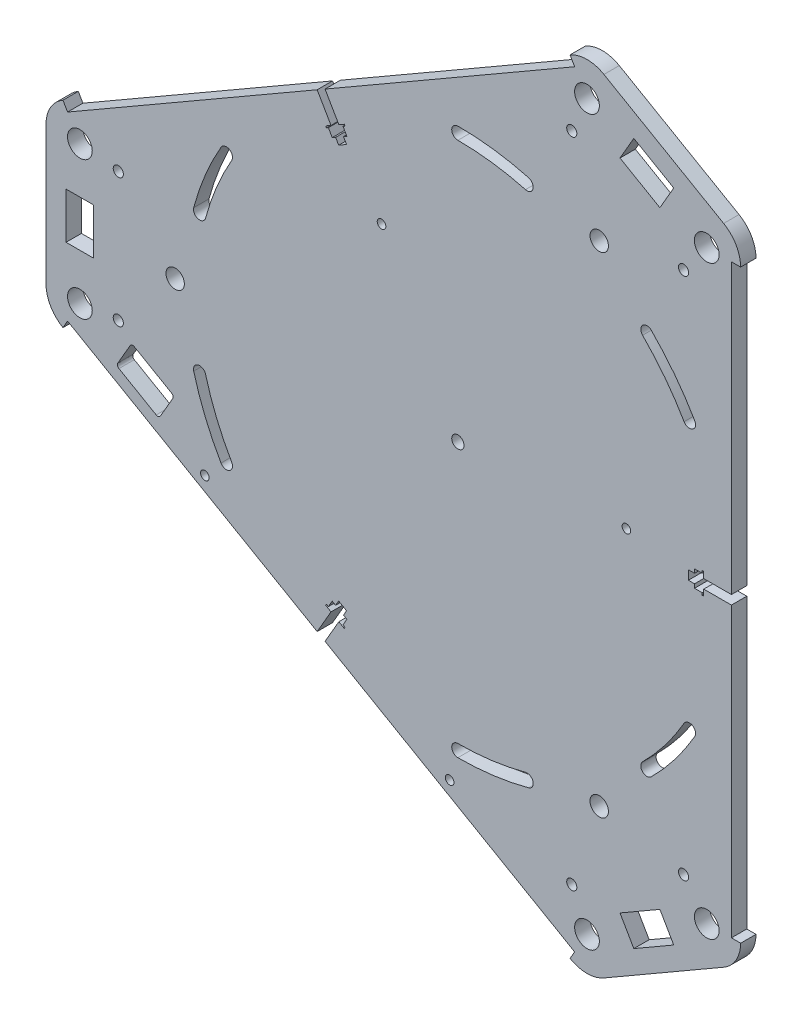
SolidWorks part; units mm, degrees
material "6061-T6 Black anodised"
ref_plane "Front Plane" through (0, 0, 0) normal (0, 0, 1) x (1, 0, 0)
ref_plane "Top Plane" through (0, 0, 0) normal (0, 1, 0) x (1, 0, 0)
ref_plane "Right Plane" through (0, 0, 0) normal (1, 0, 0) x (0, 0, -1)
sketch "Sketch1" plane through (0, 0, 0) normal (0, 0, 1) x (1, 0, 0)
  line L0 (0, 0) -> (-123, 0) construction
  line L1 (-123, 22.5) -> (-123, -22.5) construction
  line L2 (-131.025, 22.4815) -> (-131.025, -22.5) construction
  line L3 (0, 0) -> (61.5, 106.5211) construction
  line L4 (0, 0) -> (61.5, -106.5211) construction
  line L5 (42.0144, 117.7711) -> (80.9856, 95.2711) construction
  line L6 (80.9856, -95.2711) -> (42.0144, -117.7711) construction
  line L7 (46.0269, 124.721) -> (84.9981, 102.221) construction
  line L8 (84.9981, -102.221) -> (46.0269, -124.721) construction
  line L9 (-127.0125, 29.4499) -> (38.0019, 124.721)
  line L10 (89.0106, 95.2711) -> (89.0106, -95.2711)
  line L11 (38.0019, -124.721) -> (-127.0125, -29.4498)
  line L12 (70.2452, 106.6682) -> (65.7452, 98.874)
  line L13 (-127.5, -7.5) -> (-118.5, -7.5)
  line L14 (-127.5, -7.5) -> (-127.5, 7.5)
  line L15 (-127.5, 7.5) -> (-118.5, 7.5)
  line L16 (-118.5, -7.5) -> (-118.5, 7.5)
  line L17 (-127.5, -7.5) -> (-118.5, 7.5) construction
  line L18 (-127.5, 7.5) -> (-118.5, -7.5) construction
  line L19 (52.7548, 106.374) -> (65.7452, 98.874)
  line L20 (57.2548, 114.1682) -> (52.7548, 106.374)
  line L21 (57.2548, 114.1682) -> (70.2452, 106.6682)
  line L22 (57.2548, -114.1682) -> (52.7548, -106.374)
  line L23 (65.7452, -98.874) -> (52.7548, -106.374)
  line L24 (70.2452, -106.6682) -> (65.7452, -98.874)
  line L25 (70.2452, -106.6682) -> (57.2548, -114.1682)
  line L26 (-110.5, 21) -> (-110.5, -21) construction
  line L27 (35.0646, 121.7836) -> (11.1397, 80.3446) construction
  line L28 (11.1397, 80.3446) -> (-75.1503, 30.525) construction
  line L29 (-75.1503, 30.525) -> (-123, 30.525) construction
  line L30 (-75.1503, -30.525) -> (-123, -30.525) construction
  line L31 (-75.1503, -30.525) -> (11.1397, -80.3446) construction
  line L32 (11.1397, -80.3446) -> (35.0646, -121.7836) construction
  line L33 (86.4354, -88.6605) -> (64.0106, -49.8196) construction
  line L34 (64.0106, -49.8196) -> (64.0106, 49.8196) construction
  line L35 (64.0106, 49.8196) -> (86.4354, 88.6605) construction
  line L36 (11.1397, 80.3446) -> (64.0106, 49.8196) construction
  line L37 (64.0106, -49.8196) -> (11.1397, -80.3446) construction
  line L38 (-75.1503, -30.525) -> (-75.1503, 30.525) construction
  line L39 (-127.0125, -29.4498) -> (-128.5125, -32.0479)
  line L40 (-134.025, -22.5) -> (-134.025, 22.5)
  line L41 (-127.0125, 29.4499) -> (-128.5125, 32.0479)
  line L42 (38.0019, -124.721) -> (36.5019, -127.319)
  line L43 (89.0106, 95.2711) -> (92.0106, 95.2711)
  line L44 (38.0019, 124.721) -> (36.5019, 127.319)
  line L45 (47.53, -127.3173) -> (86.9806, -104.5237)
  line L46 (89.0106, -95.2711) -> (92.0106, -95.2711)
  line L47 (47.5269, 127.319) -> (86.4981, 104.819)
  line L49 (-93.5, 2.5981) -> (-95, 0) construction
  line L50 (-95, 0) -> (-93.5, -2.5981) construction
  line L51 (-93.5, -2.5981) -> (-90.5, -2.5981) construction
  line L52 (-90.5, -2.5981) -> (-89, 0) construction
  line L53 (-89, 0) -> (-90.5, 2.5981) construction
  line L54 (-90.5, 2.5981) -> (-93.5, 2.5981) construction
  circle A0 centre (-123, 22.5) radius 4.025
  circle A1 centre (-123, -22.5) radius 4.025
  arc A2 (-127.0125, 29.4499) -> (-131.025, 22.4815) centre (-123, 22.5) ccw construction
  arc A3 (-131.025, -22.5) -> (-127.0125, -29.4498) centre (-123, -22.5) ccw construction
  circle A4 centre (42.0144, 117.7711) radius 4.025
  circle A5 centre (80.9856, 95.2711) radius 4.025
  circle A6 centre (80.9856, -95.2711) radius 4.025
  circle A7 centre (42.0144, -117.7711) radius 4.025
  arc A8 (38.0019, -124.721) -> (46.0269, -124.721) centre (42.0144, -117.7711) ccw construction
  arc A9 (84.9981, -102.221) -> (89.0106, -95.2711) centre (80.9856, -95.2711) ccw construction
  arc A10 (89.0106, 95.2711) -> (84.9981, 102.221) centre (80.9856, 95.2711) ccw construction
  arc A11 (46.0269, 124.721) -> (38.0019, 124.721) centre (42.0144, 117.7711) ccw construction
  circle A12 centre (-110.5, 21) radius 1.65
  circle A13 centre (-110.5, -21) radius 1.65
  circle A14 centre (73.4365, 85.1958) radius 1.65
  circle A15 centre (37.0635, 106.1958) radius 1.65
  circle A16 centre (37.0635, -106.1958) radius 1.65
  circle A17 centre (73.4365, -85.1958) radius 1.65
  circle A18 centre (0, 0) radius 64.0106 construction
  circle A19 centre (0, 0) radius 2
  circle A20 centre (8.2272, 4.75) radius 2 construction
  circle A21 centre (8.2272, -4.75) radius 2 construction
  circle A22 centre (0, -9.5) radius 2 construction
  circle A23 centre (0, 9.5) radius 2 construction
  circle A24 centre (-8.2272, -4.75) radius 2 construction
  circle A25 centre (-8.2272, 4.75) radius 2 construction
  arc A26 (-134.025, -22.5) -> (-128.5125, -32.0479) centre (-123, -22.5) ccw
  arc A27 (-134.025, 22.5) -> (-128.5125, 32.0479) centre (-123, 22.5) cw
  arc A28 (36.5019, -127.319) -> (47.53, -127.3173) centre (42.0144, -117.7711) ccw
  arc A29 (86.9806, -104.5237) -> (92.0106, -95.2711) centre (80.9856, -95.2711) ccw
  arc A30 (92.0106, 95.2711) -> (86.4981, 104.819) centre (80.9856, 95.2711) ccw
  arc A31 (47.5269, 127.319) -> (36.5019, 127.319) centre (42.0144, 117.7711) ccw
  circle A32 centre (-92, 0) radius 3
  circle A33 centre (46, 79.6743) radius 3
  circle A34 centre (46, -79.6743) radius 3
  point P43 (0, 0)
  point P44 (-110.5, 0)
  point P57 (0, 0)
  point P84 (0, 0)
  point P86 (0, 0)
  point P111 (0, 0)
  dimension "D3" = 8.05
  dimension "D5" = 4
  dimension "D10" = 3.3
  dimension "D13" = 25
  dimension "D14" = 4
  dimension "D15" = 9.5
  dimension "D17" = 3
  dimension "D18" = 6
  dimension "D1" = 123
  dimension "D2" = 45
  dimension "D4" = 120
  dimension "D6" = 9
  dimension "D7" = 15
  dimension "D9" = 42
  dimension "D11" = 12.5
  dimension "D19" = 92
  dimension "D8" = 3
  dimension "D12" = 3
  dimension "D16" = 6
  dimension "D20" = 3
extrude "Boss-Extrude1" add sketch "Sketch1" along normal blind 5
sketch "Sketch2" plane through (0, 0, 5) normal (0, 0, 1) x (1, 0, 0)
  line L0 (0, 0) -> (-44.5053, -77.0854) construction
  line L1 (-127.0125, -29.4498) -> (38.0019, -124.721) construction
  line L2 (0, 0) -> (-44.5053, 77.0854) construction
  line L3 (38.0019, 124.721) -> (-127.0125, 29.4499) construction
  line L4 (0, 0) -> (89.0106, 0) construction
  line L5 (89.0106, -95.2711) -> (89.0106, 95.2711) construction
  line L6 (89.0106, 1.48) -> (80.0106, 1.48)
  line L7 (80.0106, 1.48) -> (80.0106, 3.5)
  line L8 (80.0106, 3.5) -> (79.5106, 3.5)
  line L9 (79.5106, 3.5) -> (79.5106, 2.75)
  line L10 (79.5106, 2.75) -> (77.0106, 2.75)
  line L11 (77.0106, 2.75) -> (77.0106, 1.48)
  line L12 (77.0106, 1.48) -> (75.0106, 1.48)
  line L13 (75.0106, 1.48) -> (75.0106, -1.48)
  line L14 (89.0106, -1.48) -> (80.0106, -1.48)
  line L15 (80.0106, -1.48) -> (80.0106, -3.5)
  line L16 (80.0106, -3.5) -> (79.5106, -3.5)
  line L17 (79.5106, -3.5) -> (79.5106, -2.75)
  line L18 (79.5106, -2.75) -> (77.0106, -2.75)
  line L19 (77.0106, -2.75) -> (77.0106, -1.48)
  line L20 (77.0106, -1.48) -> (75.0106, -1.48)
  line L21 (89.0106, -1.48) -> (89.0106, 1.48)
  line L22 (-43.2236, -77.8254) -> (-38.7236, -70.0312)
  line L23 (-38.7236, -70.0312) -> (-36.9742, -71.0412)
  line L24 (-36.9742, -71.0412) -> (-36.7242, -70.6082)
  line L25 (-36.7242, -70.6082) -> (-37.3737, -70.2332)
  line L26 (-37.3737, -70.2332) -> (-36.1237, -68.0681)
  line L27 (-36.1237, -68.0681) -> (-37.2236, -67.4331)
  line L28 (-37.2236, -67.4331) -> (-36.2236, -65.7011)
  line L29 (-36.2236, -65.7011) -> (-38.787, -64.2211)
  line L30 (-39.787, -65.9531) -> (-38.787, -64.2211)
  line L31 (-40.8869, -65.3181) -> (-39.787, -65.9531)
  line L32 (-42.1369, -67.4832) -> (-40.8869, -65.3181)
  line L33 (-42.7864, -67.1082) -> (-42.1369, -67.4832)
  line L34 (-43.0364, -67.5412) -> (-42.7864, -67.1082)
  line L35 (-41.287, -68.5512) -> (-43.0364, -67.5412)
  line L36 (-45.787, -76.3454) -> (-41.287, -68.5512)
  line L37 (-45.787, -76.3454) -> (-43.2236, -77.8254)
  line L38 (-45.787, 76.3454) -> (-41.287, 68.5512)
  line L39 (-41.287, 68.5512) -> (-43.0364, 67.5412)
  line L40 (-43.0364, 67.5412) -> (-42.7864, 67.1082)
  line L41 (-42.7864, 67.1082) -> (-42.1369, 67.4832)
  line L42 (-42.1369, 67.4832) -> (-40.8869, 65.3181)
  line L43 (-40.8869, 65.3181) -> (-39.787, 65.9531)
  line L44 (-39.787, 65.9531) -> (-38.787, 64.2211)
  line L45 (-38.787, 64.2211) -> (-36.2236, 65.7011)
  line L46 (-37.2236, 67.4331) -> (-36.2236, 65.7011)
  line L47 (-36.1237, 68.0681) -> (-37.2236, 67.4331)
  line L48 (-37.3737, 70.2332) -> (-36.1237, 68.0681)
  line L49 (-36.7242, 70.6082) -> (-37.3737, 70.2332)
  line L50 (-36.9742, 71.0412) -> (-36.7242, 70.6082)
  line L51 (-38.7236, 70.0312) -> (-36.9742, 71.0412)
  line L52 (-43.2236, 77.8254) -> (-38.7236, 70.0312)
  line L53 (-43.2236, 77.8254) -> (-45.787, 76.3454)
  point P28 (75.0106, 0)
  point P62 (0.0125, 0.0072)
  point P64 (0, 0)
  point P65 (0, 0)
  dimension "D1" = 0.5
  dimension "D2" = 2.5
  dimension "D3" = 2
  dimension "D4" = 14
  dimension "D5" = 2.96
  dimension "D6" = 7
  dimension "D7" = 5.5
  dimension "D8" = 3
extrude "Cut-Extrude1" cut sketch "Sketch2" against normal through all
sketch "Sketch3" plane through (0, 0, 5) normal (0, 0, 1) x (1, 0, 0)
  line L0 (-110.2901, -34.4857) -> (-98.1657, -41.4857)
  line L1 (-110.6561, -33.1197) -> (-106.6561, -26.1915)
  line L2 (-96.7997, -41.1197) -> (-92.7997, -34.1915)
  line L3 (-105.2901, -25.8255) -> (-93.1657, -32.8255)
  line L4 (-127.0125, -29.4498) -> (-45.787, -76.3454) construction
  line L5 (-128.5125, -32.0479) -> (-127.0125, -29.4498) construction
  line L6 (-24.8424, 48.9716) -> (-82.3425, -50.6213) construction
  line L7 (-24.8424, 48.9716) -> (54.8319, 2.9716) construction
  line L8 (-82.3425, -50.6213) -> (-2.6681, -96.6213) construction
  line L9 (54.8319, 2.9716) -> (-2.6681, -96.6213) construction
  line L10 (-24.8424, 48.9716) -> (-2.6681, -96.6213) construction
  line L11 (-82.3425, -50.6213) -> (54.8319, 2.9716) construction
  line L13 (-36.2236, -65.7011) -> (-38.787, -64.2211) construction
  line L14 (-37.5053, -64.9611) -> (0, 0) construction
  arc A0 (-110.6561, -33.1197) -> (-110.2901, -34.4857) centre (-109.7901, -33.6197) ccw
  arc A1 (-98.1657, -41.4857) -> (-96.7997, -41.1197) centre (-97.6657, -40.6197) ccw
  arc A2 (-92.7997, -34.1915) -> (-93.1657, -32.8255) centre (-93.6657, -33.6915) ccw
  arc A3 (-105.2901, -25.8255) -> (-106.6561, -26.1915) centre (-105.7901, -26.6915) ccw
  circle A4 centre (-82.3425, -50.6213) radius 1.4
  circle A5 centre (-2.6681, -96.6213) radius 1.4
  circle A6 centre (54.8319, 2.9716) radius 1.4
  circle A7 centre (-24.8424, 48.9716) radius 1.4
  point P17 (-13.7553, -23.8248)
  dimension "D3" = 1
  dimension "D8" = 2.8
  dimension "D1" = 16
  dimension "D2" = 16
  dimension "D4" = 4
  dimension "D5" = 10
  dimension "D6" = 92
  dimension "D7" = 115
extrude "Cut-Extrude2" cut sketch "Sketch3" against normal through all
sketch "Sketch4" plane through (0, 0, 5) normal (0, 0, 1) x (1, 0, 0)
  line L0 (-72, 14.5) -> (-72, -14.5) construction
  line L1 (48.5574, 55.1038) -> (23.4426, 69.6038) construction
  line L2 (23.4426, -69.6038) -> (48.5574, -55.1038) construction
  circle A0 centre (-72, 14.5) radius 1.375
  circle A1 centre (-72, -14.5) radius 1.375
  circle A2 centre (48.5574, 55.1038) radius 1.375
  circle A3 centre (23.4426, 69.6038) radius 1.375
  circle A4 centre (36, 62.3538) radius 4 construction
  circle A5 centre (23.4426, -69.6038) radius 1.375
  circle A6 centre (-72, 0) radius 4 construction
  circle A7 centre (48.5574, -55.1038) radius 1.375
  circle A8 centre (36, -62.3538) radius 4 construction
  point P21 (0, 0)
  point P24 (0, 0)
  dimension "D1" = 29
  dimension "D2" = 8
  dimension "D3" = 2.75
  dimension "D4" = 72
  dimension "D5" = 3
extrude "Cut-Extrude3" [suppressed] cut sketch "Sketch4" against normal through all
sketch "Sketch5" plane through (0, 0, 5) normal (0, 0, 1) x (1, 0, 0)
  line L0 (-104, 0) -> (0, 0) construction
  line L1 (0, 0) -> (52, 90.0666) construction
  line L2 (0, 0) -> (52, -90.0666) construction
  line L3 (-104, 0) -> (52, 90.0666) construction
  line L4 (52, 90.0666) -> (52, -90.0666) construction
  line L5 (52, -90.0666) -> (-104, 0) construction
  line L6 (89.0106, 1.48) -> (89.0106, 95.2711) construction
  circle A0 centre (-123, 22.5) radius 4.025 construction
  circle A1 centre (0, 0) radius 23 construction
  circle A2 centre (0, 0) radius 89.0106 construction
  point P0 (-104, 0)
  point P9 (11.5, 19.9186)
  point P10 (11.5, -19.9186)
  point P11 (-23, 0)
  dimension "D1" = 19
  dimension "D5" = 46
  dimension "D7" = 178.0211
  dimension "D2" = 120
  dimension "D3" = 120
  dimension "D4" = 180.1333
  dimension "D6" = 81
ref_axis "Axis1" through (0, 0, 5) along (0, 0, -1)
sketch "Sketch6" plane through (0, 0, 5) normal (0, 0, 1) x (1, 0, 0)
  line L0 (-73.6122, 42.5) -> (-77.0763, 44.5) construction
  line L1 (-92, 0) -> (0, 0) construction
  line L3 (-82.1037, 21.9996) -> (-85.9674, 23.0349) construction
  arc A0 (-77.0763, 44.5) -> (-85.9674, 23.0349) centre (0, 0) ccw
  arc A2 (-73.6122, 42.5) -> (-82.1037, 21.9996) centre (0, 0) ccw
  arc A3 (-73.6122, 42.5) -> (-77.0763, 44.5) centre (-75.3442, 43.5) ccw
  arc A4 (-85.9674, 23.0349) -> (-82.1037, 21.9996) centre (-84.0355, 22.5173) ccw
  arc A5 (-73.6122, -42.5) -> (-77.0763, -44.5) centre (-75.3442, -43.5) cw
  arc A6 (-77.0763, -44.5) -> (-85.9674, -23.0349) centre (0, 0) cw
  arc A7 (-85.9674, -23.0349) -> (-82.1037, -21.9996) centre (-84.0355, -22.5173) cw
  arc A8 (-73.6122, -42.5) -> (-82.1037, -21.9996) centre (0, 0) cw
  circle A9 centre (-92, 0) radius 3 construction
  dimension "D1" = 15
  dimension "D3" = 4
  dimension "D2" = 30
extrude "Cut-Extrude4" cut sketch "Sketch6" against normal through all
pattern_circular "CirPattern1" count 3 over 360 about axis through (0, 0, 5) along (0, 0, -1) of "Cut-Extrude4"
